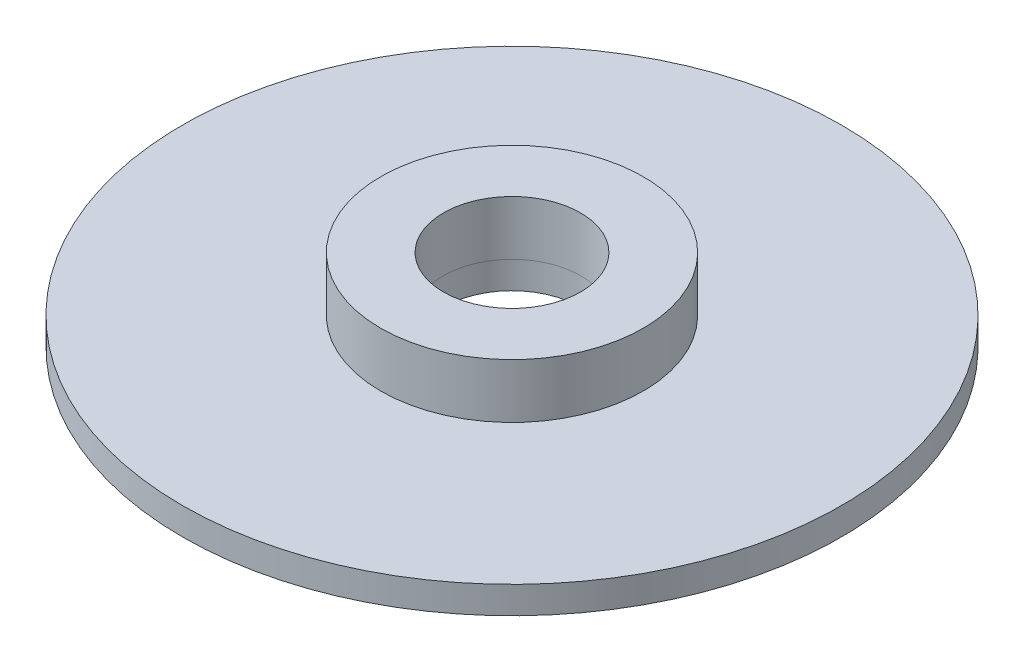
SolidWorks part; units mm, degrees
material "6061 Alloy"
ref_plane "Front Plane" through (0, 0, 0) normal (0, 0, 1) x (1, 0, 0)
ref_plane "Top Plane" through (0, 0, 0) normal (0, 1, 0) x (1, 0, 0)
ref_plane "Right Plane" through (0, 0, 0) normal (1, 0, 0) x (0, 0, -1)
sketch "Sketch1" plane through (0, 1054.464, 0) normal (0, 1, 0) x (-1, 0, 0)
  circle A0 centre (1.2041, -633.1149) radius 38.45
  circle A2 centre (1.3649, -632.8302) radius 38.45 construction
  circle A3 centre (10.3365, -639.9883) radius 1.8542 construction
  circle A4 centre (-2.5108, -643.9243) radius 1.8542 construction
  circle A5 centre (-10.2243, -632.9221) radius 1.8542 construction
  circle A6 centre (10.5632, -626.5534) radius 1.8542 construction
  circle A7 centre (-2.1441, -622.1863) radius 1.8542 construction
  circle A8 centre (1.2041, -633.1149) radius 8.001
  circle A9 centre (10.3365, -639.9883) radius 1.8542
  circle A10 centre (-2.5108, -643.9243) radius 1.8542
  circle A11 centre (-10.2243, -632.9221) radius 1.8542
  circle A12 centre (10.5632, -626.5534) radius 1.8542
  circle A13 centre (-2.1441, -622.1863) radius 1.8542
  dimension "D1" = 16.002
extrude "Boss-Extrude1" add sketch "Sketch1" against normal blind 3.175
sketch "Sketch2" plane through (0, 1054.464, 0) normal (0, 1, 0) x (1, 0, 0)
  circle A0 centre (-1.2041, 633.1149) radius 8.001
  circle A1 centre (-1.2041, 633.1149) radius 15.3187
extrude "Boss-Extrude2" add sketch "Sketch2" along normal blind 6.35 separate body
